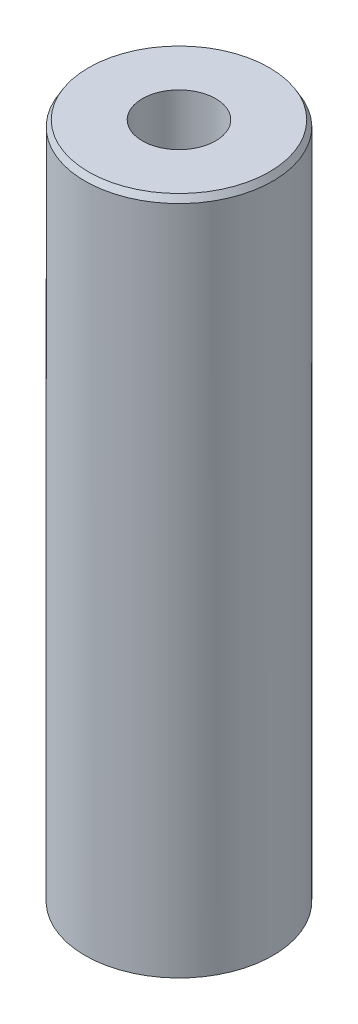
SolidWorks part; units mm, degrees
ref_plane "Front Plane" through (0, 0, 0) normal (0, 0, 1) x (1, 0, 0)
ref_plane "Top Plane" through (0, 0, 0) normal (0, 1, 0) x (1, 0, 0)
ref_plane "Right Plane" through (0, 0, 0) normal (1, 0, 0) x (0, 0, -1)
sketch "Sketch1" plane through (0, 0, 0) normal (0, 1, 0) x (1, 0, 0)
  circle A0 centre (0, 0) radius 25
  dimension "SHAFT_OD" = 50
extrude "Boss-Extrude1" add sketch "Sketch1" along normal blind 181.1066
sketch "Sketch2" plane through (0, 0, 0) normal (0, 1, 0) x (1, 0, 0)
  circle A0 centre (0, 0) radius 9.7535
  dimension "BORE_D" = 19.5071
extrude "Cut-Extrude1" cut sketch "Sketch2" along normal through all
chamfer "Chamfer1" distance 1.6482 angle 30 2 edges at (0, 181.1066, 25) (0, 0, 25) first distance on face at (0, 181.1066, 25) first distance on face at (0, 0, 9.7535)
